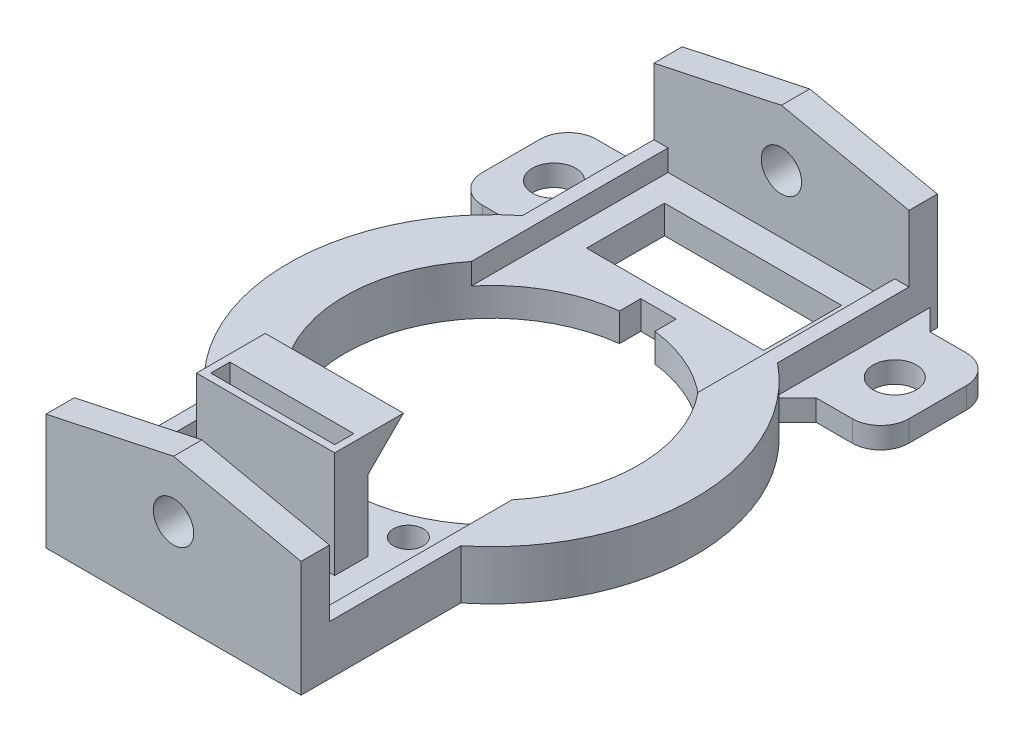
SolidWorks part; units mm, degrees
ref_plane "Front Plane" through (0, 0, 0) normal (0, 0, 1) x (1, 0, 0)
ref_plane "Top Plane" through (0, 0, 0) normal (0, 1, 0) x (1, 0, 0)
ref_plane "Right Plane" through (0, 0, 0) normal (1, 0, 0) x (0, 0, -1)
sketch "Sketch1" plane through (0, 0, 0) normal (0, 0, 1) x (1, 0, 0)
  line L3 (-18, 114.7896) -> (0, 114.7896)
  line L4 (0, 114.7896) -> (18, 114.7896)
  line L7 (0, 118.6383) -> (-38.0273, 110.5073) construction
  line L9 (38.0273, 110.5073) -> (0, 118.6383) construction
  line L11 (18, 114.7896) -> (18, 121.7896)
  line L12 (18, 121.7896) -> (16, 121.7896)
  line L13 (16, 121.7896) -> (16, 118.7896)
  line L14 (16, 118.7896) -> (-16, 118.7896)
  line L15 (-16, 118.7896) -> (-16, 121.7896)
  line L16 (-16, 121.7896) -> (-18, 121.7896)
  line L17 (-18, 121.7896) -> (-18, 114.7896)
  point P15 (0, 118.7896)
  dimension "D1" = 32
  dimension "D2" = 2
  dimension "D3" = 3
  dimension "D4" = 4
extrude "Boss-Extrude1" add sketch "Sketch1" along normal up to surface (89.8 mm away)
sketch "Sketch2" plane through (0, 114.7896, 0) normal (0, -1, 0) x (1, 0, 0)
  line L0 (18, 89.8) -> (18, 0) construction
  line L5 (-14, 54.9) -> (14, 54.9)
  line L6 (-14, 54.9) -> (-14, 34.9)
  line L7 (-14, 34.9) -> (14, 34.9)
  line L8 (14, 54.9) -> (14, 34.9)
  point P4 (0, 34.9)
  point P8 (18, 44.9)
  point P9 (14, 44.9)
  dimension "D1" = 4
  dimension "D2" = 20
extrude "Cut-Extrude1" [suppressed] cut sketch "Sketch2" against normal up to next
sketch "Sketch3" plane through (-18, 0, 0) normal (-1, 0, 0) x (0, 0, 1)
  line L0 (89.8, 121.7896) -> (0, 121.7896) construction
  line L1 (40.65, 118.7896) -> (49.15, 118.7896)
  line L2 (40.65, 118.7896) -> (40.65, 121.7896)
  line L3 (40.65, 121.7896) -> (49.15, 121.7896)
  line L4 (49.15, 118.7896) -> (49.15, 121.7896)
  line L5 (89.8, 118.7896) -> (0, 118.7896) construction
  point P9 (44.9, 121.7896)
  point P10 (44.9, 121.7896)
  dimension "D1" = 8.5
extrude "Cut-Extrude2" [suppressed] cut sketch "Sketch3" against normal through all
sketch "Sketch4" plane through (0, 118.7896, 0) normal (0, 1, 0) x (1, 0, 0)
  circle A0 centre (7.75, -23.25) radius 2.1 construction
  circle A4 centre (-7.75, -23.25) radius 2.1 construction
  circle A5 centre (7.75, -23.25) radius 2.1
  circle A6 centre (-7.75, -23.25) radius 2.1
extrude "Cut-Extrude3" [suppressed] cut sketch "Sketch4" against normal through all
ref_plane "Plane2" through (0, 0, 44.9) normal (0, 0, -1) x (-1, 0, 0)
sketch "Sketch5" plane through (0, 0, 0) normal (0, 0, 1) x (1, 0, 0)
  line L0 (-18, 114.7896) -> (-18, 131.1512)
  line L1 (-56.4, 122.9405) -> (0, 135) construction
  line L2 (-18, 131.1512) -> (0, 135)
  line L3 (0, 135) -> (18, 131.1512)
  line L4 (0, 135) -> (56.4, 122.9405) construction
  line L5 (18, 131.1512) -> (18, 114.7896)
  line L6 (18, 114.7896) -> (-18, 114.7896)
  line L7 (0.6273, 134.8659) -> (54.0273, 123.4479) construction
  line L8 (-54.0273, 123.4479) -> (-0.6273, 134.8659) construction
  circle A0 centre (0, 127) radius 2.85
  dimension "D1" = 5.7
  dimension "D2" = 8
extrude "Boss-Extrude2" add sketch "Sketch5" along normal blind 4
mirror "Mirror1" about plane through (0, 0, 44.9) normal (0, 0, -1) of "Boss-Extrude2"
sketch "Sketch6" plane through (0, 118.7896, 0) normal (0, 1, 0) x (1, 0, 0)
  line L1 (12.5, -19) -> (-12.5, -19)
  line L2 (12.5, -19) -> (12.5, -8)
  line L3 (12.5, -8) -> (-12.5, -8)
  line L4 (-12.5, -19) -> (-12.5, -8)
  point P4 (0, -8)
  dimension "D1" = 11
  dimension "D2" = 25
  dimension "D3" = 8
extrude "Cut-Extrude4" cut sketch "Sketch6" against normal through all
sketch "Sketch8" plane through (0, 118.7896, 0) normal (0, 1, 0) x (1, 0, 0)
  line L0 (16, -85.8) -> (-16, -85.8) construction
  line L1 (8.75, -75.8) -> (-8.75, -75.8)
  line L2 (8.75, -75.8) -> (8.75, -73.1)
  line L3 (8.75, -73.1) -> (-8.75, -73.1)
  line L4 (-8.75, -75.8) -> (-8.75, -73.1)
  line L5 (0, -89.8) -> (53.4, -89.8) construction
  line L6 (9.75, -72.1) -> (-9.75, -72.1)
  line L7 (-9.75, -76.8) -> (-9.75, -72.1)
  line L8 (9.75, -76.8) -> (-9.75, -76.8)
  line L9 (9.75, -76.8) -> (9.75, -72.1)
  point P6 (0, -85.8)
  point P7 (0, -75.8)
  dimension "D1" = 13
  dimension "D2" = 2.7
  dimension "D3" = 17.5
  dimension "D4" = 1
extrude "Boss-Extrude3" add sketch "Sketch8" along normal blind 15
sketch "Sketch9" plane through (-9.75, 0, 0) normal (-1, 0, 0) x (0, 0, 1)
  line L0 (72.1, 128.7896) -> (67.1, 133.7896)
  line L1 (72.1, 133.7896) -> (72.1, 118.7896) construction
  line L2 (67.1, 133.7896) -> (72.1, 133.7896)
  line L3 (72.1, 133.7896) -> (72.1, 128.7896)
  dimension "D1" = 5
  dimension "D2" = 45
extrude "Boss-Extrude4" add sketch "Sketch9" against normal up to surface (19.5 mm away) up to face at (9.75, 126.2896, 74.45)
sketch "Sketch13" plane through (0, 118.7896, 0) normal (0, 1, 0) x (1, 0, 0)
  line L4 (-8.75, -75.8) -> (8.75, -75.8)
  line L5 (8.75, -75.8) -> (8.75, -73.1)
  line L6 (8.75, -73.1) -> (-8.75, -73.1)
  line L7 (-8.75, -73.1) -> (-8.75, -75.8)
  line L8 (-8.75, -75.8) -> (8.75, -75.8)
  line L9 (8.75, -75.8) -> (8.75, -73.1)
  line L10 (8.75, -73.1) -> (-8.75, -73.1)
  line L11 (-8.75, -73.1) -> (-8.75, -75.8)
  dimension "D1" = 0
extrude "Cut-Extrude5" cut sketch "Sketch13" against normal through all
sketch "Sketch10" [suppressed] plane through (0, 121.7896, 0) normal (0, 1, 0) x (1, 0, 0)
  line L1 (16, -59.15) -> (18, -59.15)
  line L2 (16, -59.15) -> (16, -49.15)
  line L3 (16, -49.15) -> (18, -49.15)
  line L4 (18, -59.15) -> (18, -49.15)
  line L5 (0, -1000) -> (0, 49000) construction
  line L6 (-16, -49.15) -> (-18, -49.15)
  line L7 (-16, -59.15) -> (-16, -49.15)
  line L8 (-16, -59.15) -> (-18, -59.15)
  line L9 (-18, -59.15) -> (-18, -49.15)
  dimension "D1" = 10
extrude "Boss-Extrude5" [suppressed] add sketch "Sketch10" along normal up to surface (12 mm away)
sketch "Sketch14" plane through (0, 114.7896, 0) normal (0, 1, 0) x (1, 0, 0)
  line L0 (-18, -85.8) -> (-18, -4) construction
  line L1 (-18, -4) -> (-30.1, -4)
  line L2 (-18, -4) -> (-18, -20.1)
  line L3 (-18, -20.1) -> (-30.1, -20.1)
  line L4 (-30.1, -4) -> (-30.1, -20.1)
  circle A0 centre (-24.05, -12.05) radius 3.05
  point P9 (-30.1, -12.05)
  point P10 (-24.05, -20.1)
  dimension "D1" = 6.1
  dimension "D2" = 3
  dimension "D3" = 5
extrude "Boss-Extrude7" add sketch "Sketch14" along normal blind 3
mirror "Mirror2" about plane through (0, 0, 0) normal (1, 0, 0) of "Boss-Extrude7"
chamfer "Chamfer1" distance 3 angle 45 4 edges at (-18, 116.2896, 20.1) (-18, 116.2896, 4) (18, 116.2896, 4) (18, 116.2896, 20.1)
sketch "Sketch17" plane through (0, 118.7896, 0) normal (0, 1, 0) x (1, 0, 0)
  circle A0 centre (0, -81.15) radius 2.1
  circle A1 centre (0, -81.15) radius 2.85 construction
  dimension "D1" = 4.2
extrude "Cut-Extrude6" cut sketch "Sketch17" against normal through all
sketch "Sketch19" plane through (0, 114.7896, 0) normal (0, -1, 0) x (1, 0, 0)
  line L0 (18, 67.2537) -> (18, 55.122)
  line L2 (-16, 68.7262) -> (-16, 58.0335)
  line L3 (-18, 34.678) -> (-18, 22.5463)
  line L4 (18, 22.5463) -> (18, 34.678)
  line L6 (-18, 85.8) -> (-18, 4) construction
  line L7 (18, 85.8) -> (18, 4) construction
  line L8 (-16, 85.8) -> (-16, 4) construction
  arc A0 (-16, 58.0335) -> (-18, 34.678) centre (0, 44.9) ccw
  arc A1 (-16, 68.7262) -> (-18, 22.5463) centre (0, 44.9) ccw
  circle A2 centre (0, 44.9) radius 20.2 construction
  arc A3 (18, 22.5463) -> (18, 67.2537) centre (0, 44.9) ccw
  arc A4 (18, 34.678) -> (18, 55.122) centre (0, 44.9) ccw
  dimension "D1" = 0.5
  dimension "D2" = 8
extrude "Boss-Extrude8" add sketch "Sketch19" against normal up to surface (7 mm away) up to face at (-17, 121.7896, 44.9)
sketch "Sketch20" plane through (0, 114.7896, 0) normal (0, -1, 0) x (1, 0, 0)
  circle A0 centre (0, 44.9) radius 20.7
  arc A1 (18, 34.678) -> (18, 55.122) centre (0, 44.9) ccw construction
extrude "Cut-Extrude7" cut sketch "Sketch20" against normal up to next
fillet "Fillet1" radius 4 4 edges at (-30.1, 116.2896, 4) (-30.1, 116.2896, 20.1) (30.1, 116.2896, 4) (30.1, 116.2896, 20.1)
sketch "Sketch21" plane through (0, 118.7896, 0) normal (0, 1, 0) x (1, 0, 0)
  circle A0 centre (-10.2696, -66.9233) radius 2.1 construction
  circle A1 centre (10.2696, -66.9233) radius 2.1 construction
  circle A2 centre (-10.2696, -66.9233) radius 2.1
  circle A3 centre (10.2696, -66.9233) radius 2.1
extrude "Cut-Extrude8" cut sketch "Sketch21" against normal through all
sketch "Sketch22" plane through (0, 118.7896, 0) normal (0, 1, 0) x (1, 0, 0)
  line L0 (-1000, -44.9) -> (49000, -44.9) construction
  line L1 (-2.5, -65.4485) -> (2.5, -65.4485)
  line L2 (-2.5, -65.4485) -> (-2.5, -68.4485)
  line L3 (-2.5, -68.4485) -> (2.5, -68.4485)
  line L4 (2.5, -65.4485) -> (2.5, -68.4485)
  line L5 (2.5, -24.3515) -> (2.5, -21.3515)
  line L6 (-2.5, -21.3515) -> (2.5, -21.3515)
  line L7 (-2.5, -24.3515) -> (-2.5, -21.3515)
  line L8 (-2.5, -24.3515) -> (2.5, -24.3515)
  arc A0 (-16, -58.0335) -> (16, -58.0335) centre (0, -44.9) ccw construction
  dimension "D1" = 5
  dimension "D2" = 3
extrude "Cut-Extrude9" cut sketch "Sketch22" against normal through all
equation "\"width\"= 24"
equation "\"thk\"= 3"
equation "\"holesize\"= 4.2"
equation "\"holedistance\"= ( 20 + 12 ) / 2"
equation "\"threaded_hole\"= 3.9"
equation "\"fillet_radius\"= 2"
equation "\"ground_clearance\"= 25"
equation "\"tire_thk\"= 3"
equation "\"innerwheel_diam\" = \"wheel_diam\"-2*\"tire_thk\""
equation "\"innerwheel_thk\"= 8"
equation "\"wheel_diam\"= 2*(\"width\"/2+\"ground_clearance\")"
equation "\"coloursensor_holesize\"= 2.65"
equation "\"hole_to_edge\" = 4"
equation "\"D1@Sketch5\"=\"M4_insert_diam\""
equation "\"D1@Sketch17\"=\"holesize\""
equation "\"M4_insert_diam\"= 5.7"
